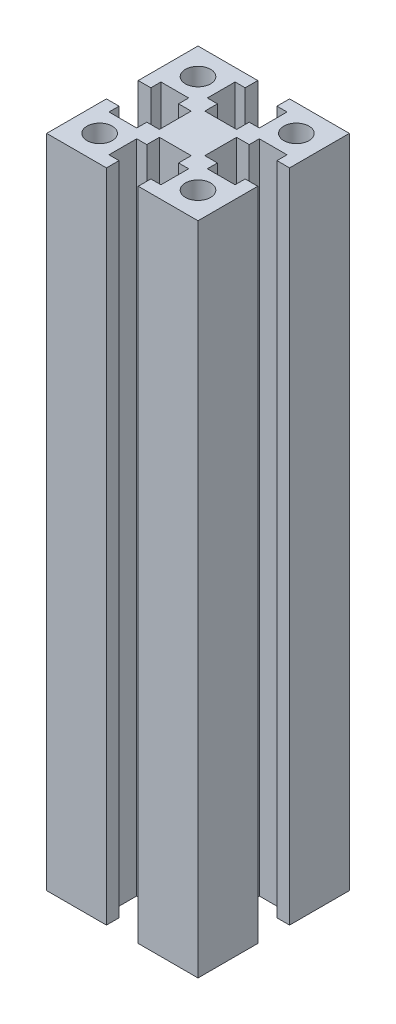
SolidWorks part; units mm, degrees
ref_plane "前视基准面" through (0, 0, 0) normal (0, 0, 1) x (1, 0, 0)
ref_plane "上视基准面" through (0, 0, 0) normal (0, 1, 0) x (1, 0, 0)
ref_plane "右视基准面" through (0, 0, 0) normal (1, 0, 0) x (0, 0, -1)
sketch "草图1" plane through (0, 0, 0) normal (0, 1, 0) x (1, 0, 0)
  line L0 (-15, -3.15) -> (-12.5, -3.15)
  line L1 (-15, 15) -> (-3.15, 15)
  line L2 (-15, 15) -> (-15, 3.15)
  line L3 (-15, -15) -> (-3.15, -15)
  line L4 (15, 15) -> (15, 3.15)
  line L5 (-15, 15) -> (15, -15) construction
  line L6 (-15, -15) -> (15, 15) construction
  line L7 (-12.5, -3.15) -> (-12.5, -5.15)
  line L8 (-12.5, -5.15) -> (-7, -5.15)
  line L9 (-7, -5.15) -> (-7, -3.15)
  line L10 (-7, -3.15) -> (-4.5, -3.15)
  line L11 (-4.5, -3.15) -> (-4.5, 3.15)
  line L12 (-4.5, 3.15) -> (-7, 3.15)
  line L13 (-7, 3.15) -> (-7, 5.15)
  line L14 (-7, 5.15) -> (-12.5, 5.15)
  line L15 (-12.5, 5.15) -> (-12.5, 3.15)
  line L16 (-12.5, 3.15) -> (-15, 3.15)
  line L17 (-15, 0) -> (-4.5, 0) construction
  line L18 (-15, -3.15) -> (-15, -15)
  line L19 (-15, 3.15) -> (-15, 0) construction
  line L20 (-15, 0) -> (-15, -3.15) construction
  line L21 (3.15, 12.5) -> (3.15, 15)
  line L22 (5.15, 12.5) -> (3.15, 12.5)
  line L23 (5.15, 7) -> (5.15, 12.5)
  line L24 (3.15, 7) -> (5.15, 7)
  line L25 (3.15, 4.5) -> (3.15, 7)
  line L26 (-3.15, 4.5) -> (3.15, 4.5)
  line L27 (-3.15, 7) -> (-3.15, 4.5)
  line L28 (-5.15, 7) -> (-3.15, 7)
  line L29 (-5.15, 12.5) -> (-5.15, 7)
  line L30 (-3.15, 12.5) -> (-5.15, 12.5)
  line L31 (-3.15, 15) -> (-3.15, 12.5)
  line L32 (12.5, -3.15) -> (15, -3.15)
  line L33 (12.5, -5.15) -> (12.5, -3.15)
  line L34 (7, -5.15) -> (12.5, -5.15)
  line L35 (7, -3.15) -> (7, -5.15)
  line L36 (4.5, -3.15) -> (7, -3.15)
  line L37 (4.5, 3.15) -> (4.5, -3.15)
  line L38 (7, 3.15) -> (4.5, 3.15)
  line L39 (7, 5.15) -> (7, 3.15)
  line L40 (12.5, 5.15) -> (7, 5.15)
  line L41 (12.5, 3.15) -> (12.5, 5.15)
  line L42 (15, 3.15) -> (12.5, 3.15)
  line L43 (-3.15, -12.5) -> (-3.15, -15)
  line L44 (-5.15, -12.5) -> (-3.15, -12.5)
  line L45 (-5.15, -7) -> (-5.15, -12.5)
  line L46 (-3.15, -7) -> (-5.15, -7)
  line L47 (-3.15, -4.5) -> (-3.15, -7)
  line L48 (3.15, -4.5) -> (-3.15, -4.5)
  line L49 (3.15, -7) -> (3.15, -4.5)
  line L50 (5.15, -7) -> (3.15, -7)
  line L51 (5.15, -12.5) -> (5.15, -7)
  line L52 (3.15, -12.5) -> (5.15, -12.5)
  line L53 (3.15, -15) -> (3.15, -12.5)
  line L54 (3.15, 15) -> (15, 15)
  line L55 (15, -3.15) -> (15, -15)
  line L56 (3.15, -15) -> (15, -15)
  line L57 (-5.15, -9.75) -> (-15, -9.75) construction
  line L58 (-9.75, -5.15) -> (-9.75, -15) construction
  circle A0 centre (-9.75, -9.75) radius 2.5
  circle A1 centre (-9.75, 9.75) radius 2.5
  circle A2 centre (9.75, 9.75) radius 2.5
  circle A3 centre (9.75, -9.75) radius 2.5
  point P0 (0, 0)
  point P59 (0, 0)
  point P72 (0, 0)
  dimension "D1" = 5
  dimension "D2" = 6.3
  dimension "D3" = 10.3
  dimension "D4" = 2.5
  dimension "D5" = 5.5
  dimension "D6" = 10.5
  dimension "D7" = 30
  dimension "D8" = 4
  dimension "D9" = 4
extrude "凸台-拉伸1" add sketch "草图1" along normal mid plane 360
sketch "草图2" plane through (0, 180, 0) normal (0, 1, 0) x (1, 0, 0)
  circle A0 centre (0, 0) radius 82.2505
extrude "切除-拉伸1" cut sketch "草图2" against normal blind 10
sketch "草图3" plane through (0, -180, 0) normal (0, -1, 0) x (1, 0, 0)
  circle A0 centre (0.2164, -1.772) radius 47.3598
extrude "切除-拉伸2" cut sketch "草图3" against normal blind 200
sketch "草图4" plane through (0, 20, 0) normal (0, -1, 0) x (1, 0, 0)
  circle A0 centre (-1.2874, -1.5436) radius 50.0559
extrude "切除-拉伸3" cut sketch "草图4" against normal blind 30
sketch "草图5" plane through (0, 50, 0) normal (0, -1, 0) x (1, 0, 0)
  circle A0 centre (-0.9794, 0.8642) radius 35.7767
extrude "切除-拉伸4" cut sketch "草图5" against normal blind 40
extrude "凸台-拉伸2" add sketch "草图1<3>" along normal blind 200
sketch "草图1<3>" plane through (0, 0, 0) normal (0, 1, 0) x (1, 0, 0) same geometry as "草图1"
sketch "草图6" plane through (0, 200, 0) normal (0, 1, 0) x (1, 0, 0)
  circle A0 centre (-0.6668, 0.5001) radius 45.5084
extrude "切除-拉伸5" cut sketch "草图6" against normal blind 50
sketch "草图7" plane through (0, 150, 0) normal (0, 1, 0) x (1, 0, 0)
  circle A1 centre (0, -1.2412) radius 85.2515
extrude "切除-拉伸7" cut sketch "草图7" against normal blind 20
equation "\"零件重量\"= \"SW-质量\" / 1000"
